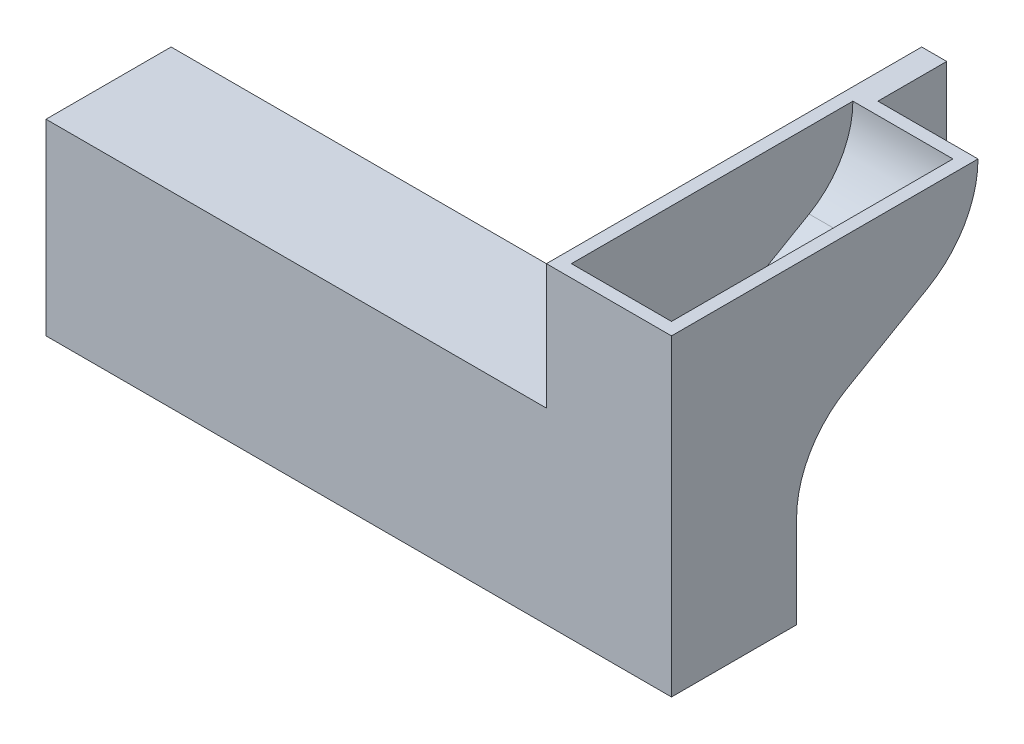
SolidWorks part; units mm, degrees
ref_plane "Front Plane" through (0, 0, 0) normal (0, 0, 1) x (1, 0, 0)
ref_plane "Top Plane" through (0, 0, 0) normal (0, 1, 0) x (1, 0, 0)
ref_plane "Right Plane" through (0, 0, 0) normal (1, 0, 0) x (0, 0, -1)
sketch "Sketch1" plane through (0, 0, 0) normal (0, 1, 0) x (1, 0, 0)
  line L0 (-20, 0) -> (20, 0)
  line L1 (20, 0) -> (20, -10)
  line L2 (20, -10) -> (-20, -10)
  line L3 (-20, -10) -> (-20, 0)
  dimension "D1" = 40
  dimension "D2" = 10
extrude "Boss-Extrude1" add sketch "Sketch1" along normal blind 15
sketch "Sketch2" plane through (20, 0, 0) normal (1, 0, 0) x (0, 0, -1)
  line L0 (-10, 0) -> (-10, 25)
  line L1 (-10, 25) -> (14.5, 25)
  line L2 (10.5, 18.0718) -> (4, 14.319)
  line L3 (0, 15) -> (0, 0) construction
  line L4 (0, 7.3908) -> (0, 0)
  line L5 (0, 0) -> (-10, 0)
  line L6 (-10, 15) -> (0, 15) construction
  arc A0 (14.5, 25) -> (10.5, 18.0718) centre (6.5, 25) cw
  arc A1 (4, 14.319) -> (0, 7.3908) centre (8, 7.3908) ccw
  dimension "D4" = 8
  dimension "D1" = 24.5
  dimension "D2" = 60
  dimension "D3" = 10
extrude "Boss-Extrude2" add sketch "Sketch2" along normal blind 10
sketch "Sketch3" plane through (20, 0, 0) normal (-1, 0, 0) x (0, 0, 1)
  line L0 (-5.1795, 15) -> (-20, 15)
  line L1 (-20, 15) -> (-20, 25)
  line L2 (-20, 25) -> (-14.5, 25)
  line L3 (-4, 14.319) -> (-10.5, 18.0718) construction
  line L4 (-5.1795, 15) -> (-10.5, 18.0718)
  line L5 (10, 15) -> (0, 15) construction
  line L6 (10, 25) -> (10, 15) construction
  arc A0 (-14.5, 25) -> (-10.5, 18.0718) centre (-6.5, 25) ccw construction
  arc A1 (-14.5, 25) -> (-10.5, 18.0718) centre (-6.5, 25) ccw
  dimension "D1" = 30
extrude "Boss-Extrude3" add sketch "Sketch3" against normal blind 2
shell "Shell1" thickness 1 removed face at (24, 25, -8.1667)
fillet "Fillet1" 2 edges at (-19, 7.5, 9) (-19, 7.5, 1) type full round first side face at (10.3333, 13.3333, 9) second side face at (10.3333, 7.4636, 1) middle face at (-19, 7.5, 5)
fillet "Fillet2" [suppressed] type full round
